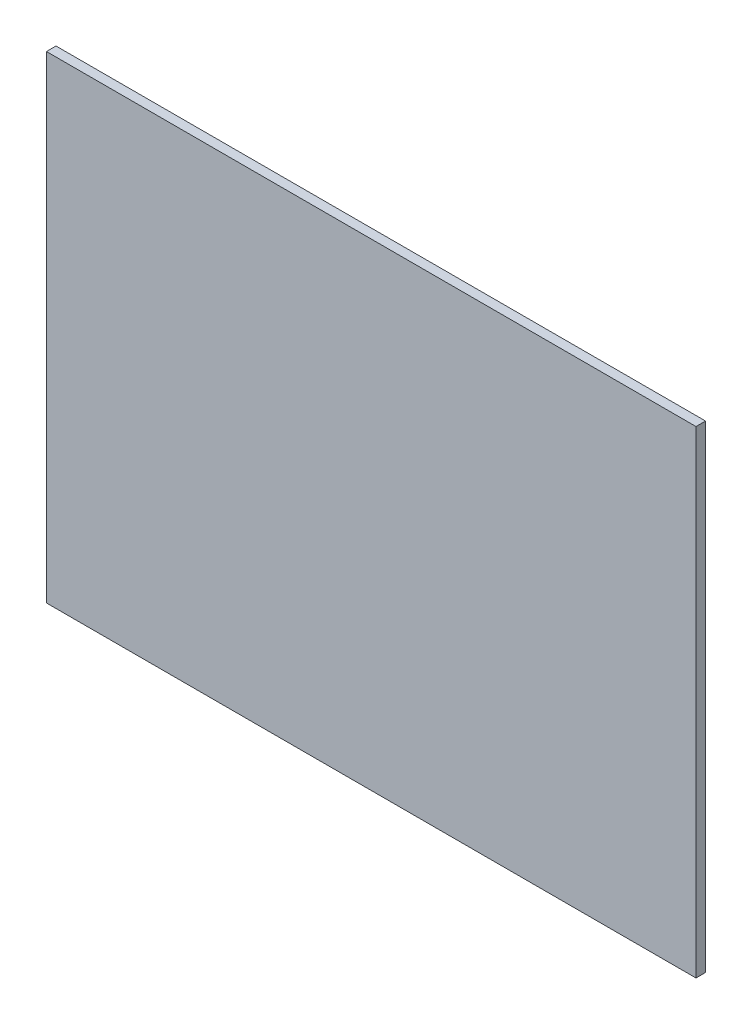
SolidWorks part; units mm, degrees
ref_plane "Front Plane" through (0, 0, 0) normal (0, 0, 1) x (1, 0, 0)
ref_plane "Top Plane" through (0, 0, 0) normal (0, 1, 0) x (1, 0, 0)
ref_plane "Right Plane" through (0, 0, 0) normal (1, 0, 0) x (0, 0, -1)
sketch "Sketch1" plane through (0, 0, 0) normal (0, 0, 1) x (1, 0, 0)
  line L1 (-170, -125) -> (170, -125)
  line L2 (-170, -125) -> (-170, 125)
  line L3 (-170, 125) -> (170, 125)
  line L4 (170, -125) -> (170, 125)
  line L5 (-170, -125) -> (170, 125) construction
  line L6 (-170, 125) -> (170, -125) construction
  point P0 (0, 0)
  dimension "D1" = 340
  dimension "D2" = 250
extrude "Boss-Extrude1" add sketch "Sketch1" along normal blind 5
